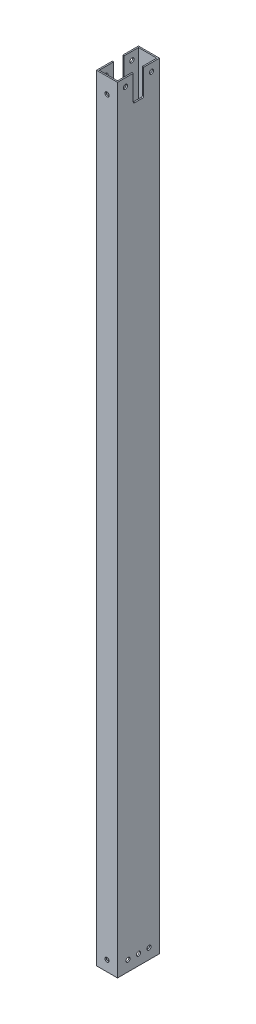
SolidWorks part; units mm, degrees
material "6061-T6 (SS)"
ref_plane "Front" through (0, 0, 0) normal (0, 0, 1) x (1, 0, 0)
ref_plane "Top" through (0, 0, 0) normal (0, 1, 0) x (1, 0, 0)
ref_plane "Right" through (0, 0, 0) normal (1, 0, 0) x (0, 0, -1)
sketch "Sketch1" plane through (0, 0, 0) normal (0, 1, 0) x (1, 0, 0)
  line L1 (12.7, 25.4) -> (-12.7, 25.4)
  line L2 (12.7, 25.4) -> (12.7, -25.4)
  line L3 (12.7, -25.4) -> (-12.7, -25.4)
  line L4 (-12.7, 25.4) -> (-12.7, -25.4)
  line L5 (12.7, 25.4) -> (-12.7, -25.4) construction
  line L6 (12.7, -25.4) -> (-12.7, 25.4) construction
  point P0 (0, 0)
  dimension "D1" = 25.4
  dimension "D2" = 50.8
extrude "Extrude-Thin1" add sketch "Sketch1" along normal blind 939.8 thin thin type one direction reverse wall 1.5875
sketch "Sketch2" plane through (-12.7, 0, 0) normal (-1, 0, 0) x (0, 0, 1)
  line L0 (-25.4, 939.8) -> (25.4, 939.8) construction
  line L1 (-6.35, 939.8) -> (6.35, 939.8)
  line L2 (-6.35, 939.8) -> (-6.35, 909.828)
  line L3 (-4.572, 908.05) -> (4.572, 908.05)
  line L4 (6.35, 939.8) -> (6.35, 909.828)
  line L5 (-25.4, 939.8) -> (-6.35, 908.05) construction
  line L6 (25.4, 939.8) -> (6.35, 908.05) construction
  arc A0 (4.572, 908.05) -> (6.35, 909.828) centre (4.572, 909.828) ccw
  arc A1 (-6.35, 909.828) -> (-4.572, 908.05) centre (-4.572, 909.828) ccw
  dimension "D3" = 1.778
  dimension "D1" = 12.7
  dimension "D2" = 31.75
extrude "Cut-Extrude1" cut sketch "Sketch2" against normal through all
sketch "Sketch5" plane through (0, 0, 25.4) normal (0, 0, 1) x (1, 0, 0)
  line L3 (-12.7, 939.8) -> (12.7, 939.8) construction
  line L4 (-12.7, 0) -> (12.7, 0) construction
  point P0 (0, 920.75)
  point P12 (0, 12.7)
  dimension "D1" = 19.05
  dimension "D2" = 12.7
hole_wizard "#10 Clearance Hole1" positions "Sketch5" profile "Sketch4" hole size "#10" standard "ANSI Inch" end condition through all
sketch "Sketch4" plane through (0, 920.75, 25.4) normal (1, 0, 0) x (0, -1, 0)
  line L0 (0, 0) -> (0, 50.8)
  line L1 (0, 50.8) -> (2.5527, 50.8)
  line L2 (2.5527, 50.8) -> (2.5527, 0)
  line L5 (2.5527, 0) -> (0, 0)
  line L11 (0, -6.35) -> (0, 107.95) construction
  dimension "Thru Hole Dia." = 5.1054
  dimension "Thru Hole Depth" = 50.8
sketch "Sketch8" plane through (-12.7, 0, 0) normal (-1, 0, 0) x (0, 0, 1)
  line L0 (-25.4, 939.8) -> (-15.875, 930.275) construction
  line L3 (25.4, 939.8) -> (15.875, 930.275) construction
  line L5 (-25.4, 939.8) -> (-6.35, 939.8) construction
  line L6 (-25.4, 939.8) -> (-25.4, 0) construction
  line L7 (-12.7, 12.7) -> (12.7, 12.7) construction
  line L9 (-25.4, 0) -> (25.4, 0) construction
  point P0 (15.875, 930.275)
  point P2 (-15.875, 930.275)
  point P20 (-12.7, 12.7)
  point P22 (0, 12.7)
  point P24 (12.7, 12.7)
  dimension "D1" = 9.525
  dimension "D2" = 9.525
  dimension "D3" = 12.7
  dimension "D4" = 12.7
hole_wizard "#10 Clearance Hole2" positions "Sketch8" profile "Sketch7" hole size "#10" standard "ANSI Inch" end condition through all
sketch "Sketch7" plane through (-12.7, 930.275, 15.875) normal (0, 1, 0) x (0, 0, 1)
  line L0 (0, 0) -> (0, 25.4)
  line L1 (0, 25.4) -> (2.5527, 25.4)
  line L2 (2.5527, 25.4) -> (2.5527, 0)
  line L5 (2.5527, 0) -> (0, 0)
  line L11 (0, -6.35) -> (0, 107.95) construction
  dimension "Thru Hole Dia." = 5.1054
  dimension "Thru Hole Depth" = 25.4
